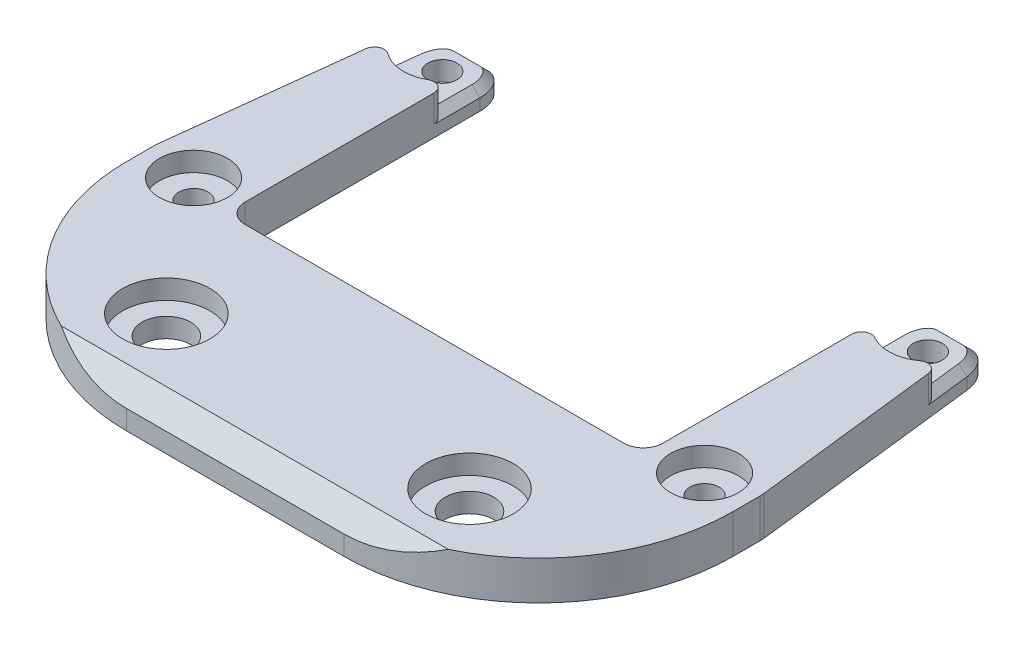
SolidWorks part; units mm, degrees
material "ABS"
ref_plane "Płaszczyzna przednia" through (0, 0, 0) normal (0, 0, 1) x (1, 0, 0)
ref_plane "Płaszczyzna górna" through (0, 0, 0) normal (0, 1, 0) x (1, 0, 0)
ref_plane "Płaszczyzna prawa" through (0, 0, 0) normal (1, 0, 0) x (0, 0, -1)
sketch "Szkic1" plane through (0, 0, 0) normal (0, 1, 0) x (1, 0, 0)
  line L0 (87.7987, 8.7776) -> (-212.2013, 8.7776) construction
  line L1 (87.7987, 20.8776) -> (-212.2013, 20.8776) construction
  line L2 (87.7987, 13.6776) -> (-212.2013, 13.6776) construction
  line L3 (1.659, 58.2776) -> (-1.1199, 58.2776)
  line L4 (-3.2709, 55.6802) -> (-6.0198, 32.0396)
  line L6 (56.3378, 32.0396) -> (53.5889, 55.6802)
  line L7 (51.4379, 58.2776) -> (48.659, 58.2776)
  line L8 (46.659, 55.4492) -> (46.659, 31.2776)
  line L9 (44.659, 29.2776) -> (5.659, 29.2776)
  line L10 (3.659, 31.2776) -> (3.659, 55.4492)
  line L11 (56.3646, 31.5776) -> (56.3646, 8.7776)
  line L12 (56.3646, 8.7776) -> (-6.0466, 8.7776)
  line L13 (25.159, 13.6776) -> (25.159, 20.8776) construction
  line L14 (25.159, 17.2776) -> (56.3646, 17.2776) construction
  line L15 (-6.0466, 31.5776) -> (-6.0466, 8.7776)
  arc A0 (-6.0198, 32.0396) -> (-6.0466, 31.5776) centre (-2.0466, 31.5776) ccw
  arc A1 (56.3646, 31.5776) -> (56.3378, 32.0396) centre (52.3646, 31.5776) ccw
  arc A2 (44.659, 29.2776) -> (46.659, 31.2776) centre (44.659, 31.2776) ccw
  arc A3 (3.659, 31.2776) -> (5.659, 29.2776) centre (5.659, 31.2776) ccw
  circle A4 centre (50.1456, 55.0768) radius 1.5
  circle A5 centre (0.1724, 55.0768) radius 1.5
  circle A6 centre (-1.1449, 30.7754) radius 1.5
  circle A7 centre (51.4629, 30.7754) radius 1.5
  circle A8 centre (40.7618, 17.2776) radius 2.5
  circle A9 centre (9.5562, 17.2776) radius 2.5
  ellipse E0 centre (-1.2843, 55.4492) end of major axis (-1.6121, 52.6302) minor radius 2 (-1.1199, 58.2776) -> (-3.2709, 55.6802) ccw
  ellipse E1 centre (51.6023, 55.4492) end of major axis (51.9301, 52.6302) minor radius 2 (53.5889, 55.6802) -> (51.4379, 58.2776) ccw
  ellipse E2 centre (48.659, 55.4492) end of major axis (48.659, 52.6207) minor radius 2 (48.659, 58.2776) -> (46.659, 55.4492) ccw
  ellipse E3 centre (1.659, 55.4492) end of major axis (1.659, 52.6207) minor radius 2 (3.659, 55.4492) -> (1.659, 58.2776) ccw
  point P67 (25.159, 8.7776)
extrude "Dodanie-wyciągnięcie1" add sketch "Szkic1" along normal blind 4
fillet "Zaokrąglenie1" radius 20 2 edges at (-6.0466, 2, -8.7776) (56.3646, 2, -8.7776)
sketch "Szkic2" plane through (0, 4, 0) normal (0, 1, 0) x (1, 0, 0)
  circle A0 centre (51.4629, 30.7754) radius 3.5
  circle A1 centre (50.1456, 55.0768) radius 4
  circle A2 centre (0.1724, 55.0768) radius 4
  circle A3 centre (-1.1449, 30.7754) radius 3.5
  circle A4 centre (9.5562, 17.2776) radius 4.5
  circle A5 centre (40.7618, 17.2776) radius 4.5
extrude "Wytnij-wyciągnięcie1" cut sketch "Szkic2" against normal blind 2
fillet "Zaokrąglenie2" radius 1 4 edges at (-3.52, 3, -53.5385) (3.659, 3, -53.1163) (46.659, 3, -53.1163) (53.838, 3, -53.5385)
chamfer "Sfazowanie1" distance 2 angle 45 1 edges at (25.159, 4, -8.7776) tangent propagation no
chamfer "Sfazowanie2" distance 0.8 angle 45 10 edges at (3.659, 2, -53.0941) (-3.533, 2, -53.4266) (3.0732, 2, -57.4492) (-2.5232, 2, -57.5292) (0.2696, 2, -58.2776) (53.851, 2, -53.4266) (46.659, 2, -53.0941) (52.8412, 2, -57.5292) (47.2448, 2, -57.4492) (50.0484, 2, -58.2776)
